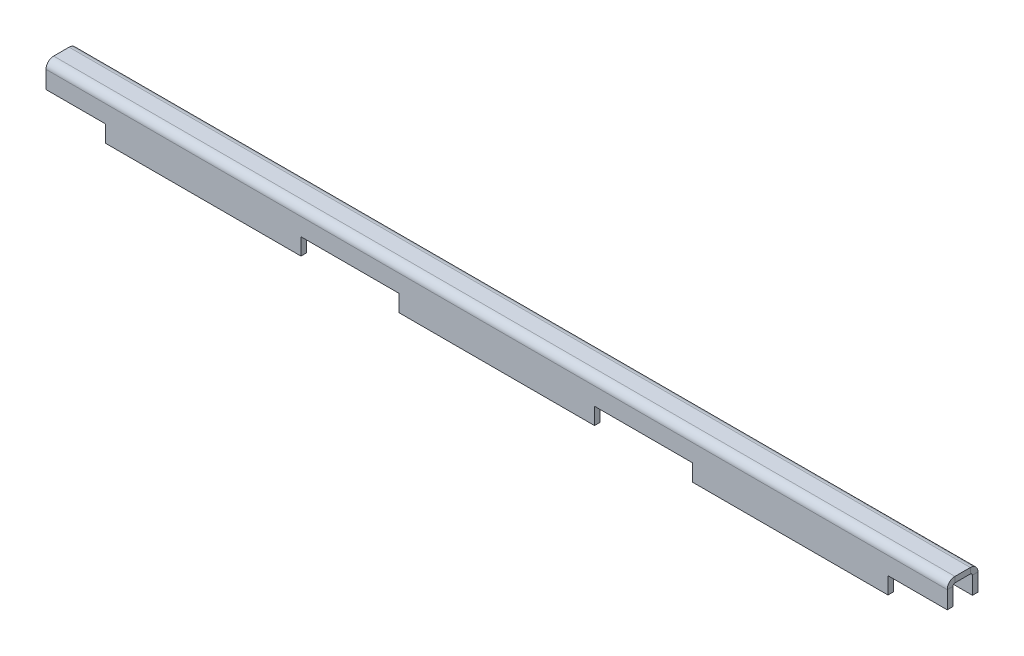
SolidWorks part; units mm, degrees
note: The reader was unsure of these and kept them because the rebuilt part matched: flange length of "Edge-Flange1".
material "ASTM A36 Steel"
ref_plane "Front Plane" through (0, 0, 0) normal (0, 0, 1) x (1, 0, 0)
ref_plane "Top Plane" through (0, 0, 0) normal (0, 1, 0) x (1, 0, 0)
ref_plane "Right Plane" through (0, 0, 0) normal (1, 0, 0) x (0, 0, -1)
sketch "Sketch2" plane through (0, 0, 0) normal (0, 1, 0) x (1, 0, 0)
  line L1 (-161.2, 5.5) -> (161.2, 5.5)
  line L2 (-161.2, 5.5) -> (-161.2, -5.5)
  line L3 (-161.2, -5.5) -> (161.2, -5.5)
  line L4 (161.2, 5.5) -> (161.2, -5.5)
  line L5 (-161.2, 5.5) -> (161.2, -5.5) construction
  line L6 (-161.2, -5.5) -> (161.2, 5.5) construction
  point P0 (0, 0)
  dimension "D1" = 322.4
  dimension "D2" = 11
base flange "Base-Flange1" sketch "Sketch2" thickness 2 reverse thickness direction no parameters "D1"=0.7366
edge flange "Edge-Flange1" sketch "Sketch11" flange profiles "Sketch11", "Sketch12" flange angle 90 flange length 9 flange position material inside bend radius 0.7366 thickness 2 relief rectangular parameters "D6"=10, "D8"=1
sketch "Sketch11" plane through (0, -2, 5.5) normal (0, 0, 1) x (-1, 0, 0)
  line L0 (161.2, 0) -> (-161.2, 0) construction
  line L1 (161.2, 0) -> (-161.2, 0)
  line L2 (-161.2, 0) -> (-161.2, 7)
  line L3 (-161.2, 7) -> (161.2, 7)
  line L4 (161.2, 7) -> (161.2, 0)
sketch "Sketch12" plane through (0, -2, -5.5) normal (0, 0, -1) x (1, 0, 0)
  line L0 (161.2, 0) -> (-161.2, 0) construction
  line L1 (161.2, 0) -> (-161.2, 0)
  line L2 (-161.2, 0) -> (-161.2, 7)
  line L3 (-161.2, 7) -> (161.2, 7)
  line L4 (161.2, 7) -> (161.2, 0)
bend "EdgeBend1" bend radius 0.7366 bend angle 90 parameters "D5"=1
bend "EdgeBend2" bend radius 0.7366 bend angle 90 parameters "D5"=2
sketch "Sketch15" plane through (0, 0, -5.5) normal (0, 0, -1) x (-1, 0, 0)
  line L0 (-161.2, -9) -> (161.2, -9) construction
  line L1 (-140, -9) -> (-70, -9)
  line L2 (-140, -9) -> (-140, -15)
  line L3 (-140, -15) -> (-70, -15)
  line L4 (-70, -9) -> (-70, -15)
  line L5 (0, 46.1369) -> (0, -97.287) construction
  line L6 (-35, -9) -> (35, -9)
  line L7 (-35, -9) -> (-35, -15)
  line L8 (-35, -15) -> (35, -15)
  line L9 (35, -9) -> (35, -15)
  line L10 (70, -9) -> (140, -9)
  line L11 (70, -9) -> (70, -15)
  line L12 (70, -15) -> (140, -15)
  line L13 (140, -9) -> (140, -15)
  dimension "D1" = 70
  dimension "D2" = 35
  dimension "D3" = 35
  dimension "D4" = 6
base flange "Tab1" sketch "Sketch15" thickness 2 reverse thickness direction no parameters "D1"=0.7366
mirror "Mirror1" about plane through (0, 0, 0) normal (0, 0, 1) of "Tab1"
sketch "Bend-Lines1" [suppressed] plane through (0, 0, 0) normal (0, 1, 0) x (1, 0, 0)
sketch "Bounding-Box1" [suppressed] plane through (0, 0, 0) normal (0, 1, 0) x (1, 0, 0)
sheet metal parameters "Sheet-Metal1" thickness 2 parameters "D1"=0.7366
flat pattern "Flat-Pattern1" [suppressed]
sketch "Bend-Lines2" plane through (0, 0, 0) normal (0, 1, 0) x (1, 0, 0)
sketch3d "Bounding-Box2" [suppressed]
  line L0 (-161.2, -5.5, 0) -> (161.2, -5.5, 0) construction
  line L1 (-161.2, 5.5, 0) -> (161.2, 5.5, 0) construction
  line L2 (-161.2, -5.5, 0) -> (-161.2, 5.5, 0) construction
  line L3 (161.2, -5.5, 0) -> (161.2, 5.5, 0) construction
sheet metal parameters "Sheet-Metal2" thickness 2 parameters "D1"=0.7366
flat pattern "Flat-Pattern1"
sketch "Bend-Lines2" plane through (0, 0, 0) normal (0, 1, 0) x (1, 0, 0)
  line L0 (161.2, 4.1273) -> (-161.2, 4.1273) construction
  line L1 (-161.2, -4.1273) -> (161.2, -4.1273) construction
  line L2 (161.2, 4.1273) -> (-161.2, 4.1273) construction
  line L3 (-161.2, -4.1273) -> (161.2, -4.1273) construction
sketch3d "Bounding-Box2" [suppressed]
  line L0 (161.2, -32.7546, 0) -> (-161.2, -32.7546, 0) construction
  line L1 (161.2, 32.7546, 0) -> (-161.2, 32.7546, 0) construction
  line L2 (161.2, -32.7546, 0) -> (161.2, 32.7546, 0) construction
  line L3 (-161.2, -32.7546, 0) -> (-161.2, 32.7546, 0) construction
bend of the flat pattern "Flatten-<EdgeBend1>1"
bend of the flat pattern "Flatten-<EdgeBend2>1"
sheet metal parameters "Sheet-Metal3" thickness 2 parameters "D1"=0.7366
flat pattern "Flat-Pattern3"
sketch "Bend-Lines3" plane through (0, 0, 0) normal (0, 1, 0) x (1, 0, 0)
  line L0 (161.2, 4.1273) -> (-161.2, 4.1273) construction
  line L1 (-161.2, -4.1273) -> (161.2, -4.1273) construction
  line L2 (161.2, 4.1273) -> (-161.2, 4.1273) construction
  line L3 (-161.2, -4.1273) -> (161.2, -4.1273) construction
sketch3d "Bounding-Box3" [suppressed]
  line L0 (161.2, -32.7546, 0) -> (-161.2, -32.7546, 0) construction
  line L1 (161.2, 38.7546, 0) -> (-161.2, 38.7546, 0) construction
  line L2 (161.2, -32.7546, 0) -> (161.2, 38.7546, 0) construction
  line L3 (-161.2, -32.7546, 0) -> (-161.2, 38.7546, 0) construction
bend of the flat pattern "Flatten-<EdgeBend2>2"
bend of the flat pattern "Flatten-<EdgeBend1>2"
sheet metal parameters "Sheet-Metal4" thickness 2 parameters "D1"=0.7366
flat pattern "Flat-Pattern3"
sketch "Bend-Lines3" plane through (0, 0, 0) normal (0, 1, 0) x (1, 0, 0)
  line L0 (161.2, 4.1273) -> (-161.2, 4.1273) construction
  line L1 (-161.2, -4.1273) -> (161.2, -4.1273) construction
  line L2 (161.2, 4.1273) -> (-161.2, 4.1273) construction
  line L3 (-161.2, -4.1273) -> (161.2, -4.1273) construction
sketch3d "Bounding-Box3" [suppressed]
  line L0 (161.2, -17.7546, 0) -> (-161.2, -17.7546, 0) construction
  line L1 (161.2, 17.7546, 0) -> (-161.2, 17.7546, 0) construction
  line L2 (161.2, -17.7546, 0) -> (161.2, 17.7546, 0) construction
  line L3 (-161.2, -17.7546, 0) -> (-161.2, 17.7546, 0) construction
bend of the flat pattern "Flatten-<EdgeBend2>2"
bend of the flat pattern "Flatten-<EdgeBend1>2"
